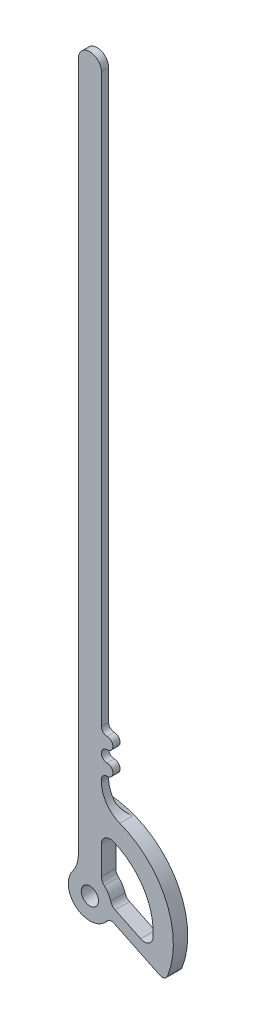
SolidWorks part; units mm, degrees
material "A2017"
ref_plane "正面" through (0, 0, 0) normal (0, 0, 1) x (1, 0, 0)
ref_plane "平面" through (0, 0, 0) normal (0, 1, 0) x (1, 0, 0)
ref_plane "右側面" through (0, 0, 0) normal (1, 0, 0) x (0, 0, -1)
sketch "ｽｹｯﾁ1" plane through (0, 0, 0) normal (0, 0, 1) x (1, 0, 0)
  line L0 (2.7026, -1.3022) -> (26.1253, -12.5884) construction
  line L1 (0, 0) -> (2.7026, -1.3022) construction
  line L2 (0, 7.5) -> (0, 29)
  line L3 (6.7565, -3.2556) -> (26.1253, -12.5884)
  arc A0 (26.1253, -12.5884) -> (0, 29) centre (0, 0) ccw
  circle A2 centre (22.0836, -12.75) radius 1.9 construction
  circle A3 centre (0, 0) radius 3
  arc A4 (0, 7.5) -> (6.7565, -3.2556) centre (0, 0) ccw
  point P0 (27.1602, -10.1649)
  dimension "D1" = 58
  dimension "D2" = 15
  dimension "D3" = 6
extrude "ﾎﾞｽ - 押し出し1" add sketch "ｽｹｯﾁ1" along normal blind 5
ref_axis "軸1" through (0, 0, -0.25) along (0, 0, 1)
sketch "ｽｹｯﾁ2" plane through (0, 0, 5) normal (0, 0, 1) x (1, 0, 0)
  line L0 (0, 0) -> (0, 250) construction
  line L1 (-4, 0) -> (-4, 250)
  line L2 (4, 0) -> (4, 250)
  line L3 (0, 29) -> (0, 7.5) construction
  line L4 (0, 29) -> (0, 7.5)
  line L5 (6.7565, -3.2556) -> (26.1253, -12.5884)
  line L6 (0, 29) -> (0, 7.5)
  line L7 (6.7565, -3.2556) -> (26.1253, -12.5884)
  line L8 (0, 29) -> (0, 7.5)
  arc A0 (-4, 0) -> (4, 0) centre (0, 0) ccw
  arc A1 (4, 250) -> (-4, 250) centre (0, 250) ccw
  arc A4 (0, 7.5) -> (6.7565, -3.2556) centre (0, 0) ccw
  arc A5 (26.1253, -12.5884) -> (0, 29) centre (0, 0) ccw
  arc A6 (0, 7.5) -> (-4, 6.3443) centre (0, 0) ccw
  arc A7 (4, 28.7228) -> (0, 29) centre (0, 0) ccw
  point P3 (0, 125)
  arc M8 (0, 7.5) -> (6.7565, -3.2556) centre (0, 0) ccw
  arc M10 (26.1253, -12.5884) -> (0, 29) centre (0, 0) ccw
  line M11 (0, 29) -> (0, 7.5)
  dimension "D2" = 250
  dimension "D3" = 8
  dimension "D1" = 0
extrude "ﾎﾞｽ - 押し出し2" add sketch "ｽｹｯﾁ2" against normal up to surface (5 mm away) contours L2 A1 L1 M8 M11 M10 region at (-0.0932, 135.329, 5) up to face at (8.6617, 5.4412, 0)
fillet "ﾌｨﾚｯﾄ1" radius 2 2 edges at (6.7565, -3.2556, 2.5) (26.1253, -12.5884, 2.5)
fillet "ﾌｨﾚｯﾄ2" radius 10 2 edges at (4, 28.7228, 2.5) (-4, 6.3443, 2.5)
sketch "ｽｹｯﾁ3" plane through (0, 0, 0) normal (0, 0, 1) x (1, 0, 0)
  line L3 (8.3665, -4.0314) -> (24.2567, -11.688)
  line L4 (4, 36.4005) -> (4, 250)
  line L5 (-4, 250) -> (-4, 10.5)
  line L6 (8.3665, -4.0314) -> (24.2567, -11.688)
  line L7 (4, 36.4005) -> (4, 250)
  line L8 (-4, 250) -> (-4, 10.5)
  circle A0 centre (0, 0) radius 29
  arc A1 (26.986, -10.6186) -> (10.4103, 27.0671) centre (0, 0) ccw construction
  arc A9 (24.2567, -11.688) -> (26.986, -10.6186) centre (25.1249, -9.8863) ccw
  arc A10 (26.986, -10.6186) -> (10.4103, 27.0671) centre (0, 0) ccw
  arc A11 (4, 36.4005) -> (10.4103, 27.0671) centre (14, 36.4005) ccw
  arc A12 (4, 250) -> (-4, 250) centre (0, 250) ccw
  arc A13 (-6, 4.5) -> (-4, 10.5) centre (-14, 10.5) ccw
  arc A14 (-6, 4.5) -> (5.9197, -4.6051) centre (0, 0) ccw
  arc A15 (8.3665, -4.0314) -> (5.9197, -4.6051) centre (7.4983, -5.8331) ccw
  arc A16 (24.2567, -11.688) -> (26.986, -10.6186) centre (25.1249, -9.8863) ccw
  arc A17 (26.986, -10.6186) -> (10.4103, 27.0671) centre (0, 0) ccw
  arc A18 (4, 36.4005) -> (10.4103, 27.0671) centre (14, 36.4005) ccw
  arc A19 (4, 250) -> (-4, 250) centre (0, 250) ccw
  arc A20 (-6, 4.5) -> (-4, 10.5) centre (-14, 10.5) ccw
  arc A21 (-6, 4.5) -> (5.9197, -4.6051) centre (0, 0) ccw
  arc A22 (8.3665, -4.0314) -> (5.9197, -4.6051) centre (7.4983, -5.8331) ccw
  arc M41 (-4, 250) -> (4, 250) centre (0, 250) cw
  line M42 (4, 250) -> (4, 36.4005)
  arc M43 (4, 36.4005) -> (10.4103, 27.0671) centre (14, 36.4005) ccw
  dimension "D1" = 0
sketch "ｽｹｯﾁ4" plane through (0, 0, 5) normal (0, 0, 1) x (1, 0, 0)
  line L0 (0, 0) -> (0, 22) construction
  line L1 (0, 0) -> (24.2567, -11.688) construction
  line L2 (4, 2.5128) -> (4, 22)
  line L3 (4, 2.5128) -> (25.9931, -8.0845)
  circle A0 centre (0, 0) radius 7.5
  arc A2 (-6, 4.5) -> (5.9197, -4.6051) centre (0, 0) ccw construction
  circle A3 centre (0, 0) radius 22
  dimension "D1" = 44
  dimension "D2" = 4
extrude "ｶｯﾄ - 押し出し2" cut sketch "ｽｹｯﾁ4" against normal through all contours L3 A3 L2 A0 region at (12.5707, 7.8967, 5)
fillet "ﾌｨﾚｯﾄ5" radius 3 4 edges at (4, 6.3443, 2.5) (21.2252, -5.7872, 2.5) (7.4517, 0.8495, 2.5) (4, 21.6333, 2.5)
extrude "ｶｯﾄ - 押し出し6" cut sketch "ｽｹｯﾁ3" along normal blind 2.5 contours A0 L8 M43 M41 M42 region at (0.0308, 140.3962, 0)
fillet "ﾌｨﾚｯﾄ7" radius 2 1 edges at (-4, 28.7228, 1.25)
fillet "ﾌｨﾚｯﾄ8" radius 2 2 edges at (-3.4657, 28.2867, 2.5) (4.2337, 28.6893, 2.5)
sketch "ｽｹｯﾁ9" plane through (0, 0, 5) normal (0, 0, 1) x (1, 0, 0)
  line L1 (4, 36.4005) -> (4, 250) construction
  line L2 (6, 39) -> (4, 39)
  line L3 (4, 39) -> (4, 51)
  line L4 (4, 51) -> (6, 51)
  arc A2 (6, 47) -> (6, 43) centre (6, 45) ccw
  arc A3 (6, 47) -> (6, 51) centre (6, 49) ccw
  arc A4 (6, 39) -> (6, 43) centre (6, 41) ccw
  line M22 (4, 36.4005) -> (4, 250)
  dimension "D1" = 4
  dimension "D2" = 45
extrude "ﾎﾞｽ - 押し出し3" add sketch "ｽｹｯﾁ9" against normal up to surface (2.5 mm away) contours A2 A3 L4 L3 | L2 A4 A2 M22 region at (5.7358, 48.8613, 5) region at (5.7358, 41.1387, 5) up to face at (0.5325, 105.3892, 2.5)
fillet "ﾌｨﾚｯﾄ9" radius 2 2 edges at (4, 51, 3.75) (4, 39, 3.75)
